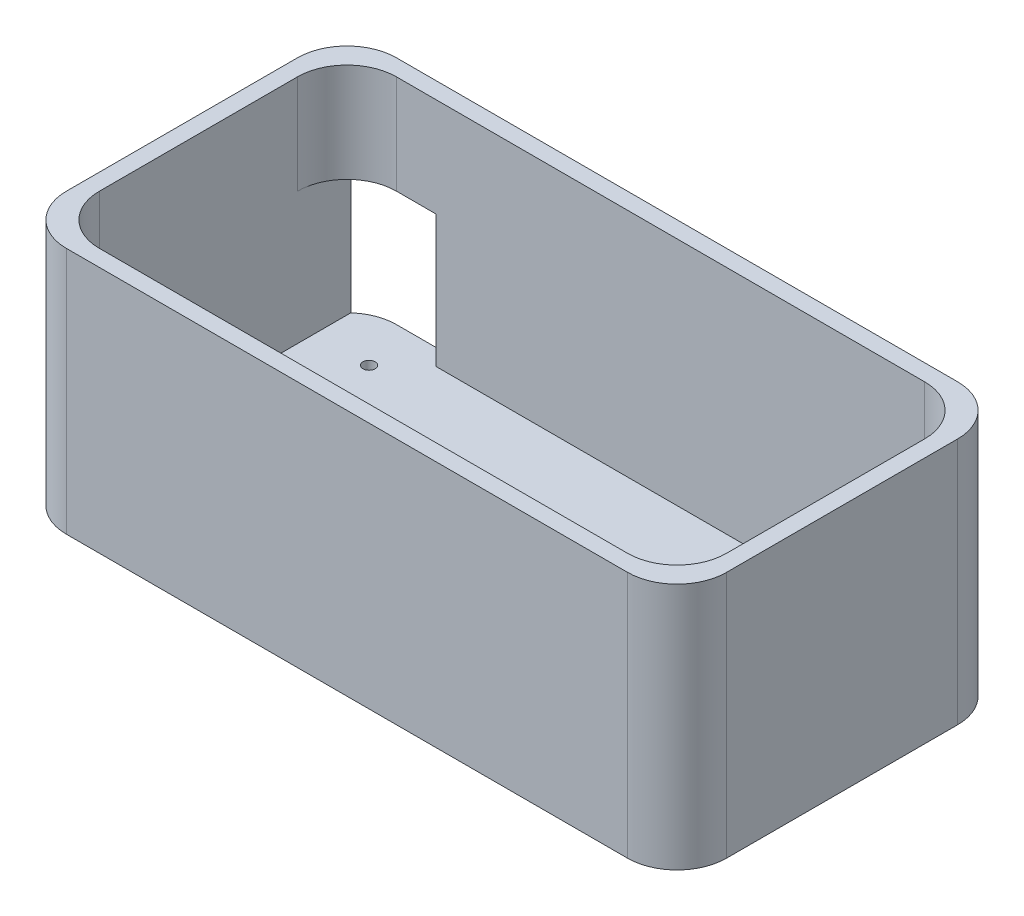
SolidWorks part; units mm, degrees
ref_plane "Front Plane" through (0, 0, 0) normal (0, 0, 1) x (1, 0, 0)
ref_plane "Top Plane" through (0, 0, 0) normal (0, 1, 0) x (1, 0, 0)
ref_plane "Right Plane" through (0, 0, 0) normal (1, 0, 0) x (0, 0, -1)
sketch "Sketch1" plane through (0, 0, 0) normal (0, 1, 0) x (1, 0, 0)
  line L1 (-100, 50) -> (100, 50)
  line L2 (-100, 50) -> (-100, -50)
  line L3 (-100, -50) -> (100, -50)
  line L4 (100, 50) -> (100, -50)
  line L5 (-100, 50) -> (100, -50) construction
  line L6 (-100, -50) -> (100, 50) construction
  point P0 (0, 0)
  dimension "D1" = 200
  dimension "D2" = 100
extrude "Boss-Extrude1" add sketch "Sketch1" along normal blind 5
sketch "Sketch2" plane through (0, 5, 0) normal (0, 1, 0) x (1, 0, 0)
  line L1 (-100, 50) -> (100, 50)
  line L2 (-100, 50) -> (-100, -50)
  line L3 (-100, -50) -> (100, -50)
  line L4 (100, 50) -> (100, -50)
  line L5 (-100, 50) -> (100, -50) construction
  line L6 (-100, -50) -> (100, 50) construction
  line L7 (-95, 45) -> (95, 45)
  line L8 (-95, 45) -> (-95, -45)
  line L9 (-95, -45) -> (95, -45)
  line L10 (95, 45) -> (95, -45)
  line L11 (-95, 45) -> (95, -45) construction
  line L12 (-95, -45) -> (95, 45) construction
  point P0 (0, 0)
  point P5 (0, 0)
  dimension "D1" = 5
  dimension "D2" = 5
extrude "Boss-Extrude2" add sketch "Sketch2" along normal blind 70
sketch "Sketch3" plane through (0, 0, -45) normal (0, 0, 1) x (1, 0, 0)
  line L1 (-95, 5) -> (-68, 5)
  line L2 (-95, 5) -> (-95, 45)
  line L3 (-95, 45) -> (-68, 45)
  line L4 (-68, 5) -> (-68, 45)
  dimension "D1" = 40
  dimension "D2" = 27
extrude "Cut-Extrude1" cut sketch "Sketch3" against normal through all
fillet "Fillet1" radius 15 8 edges at (95, 40, 45) (95, 40, -45) (100, 37.5, -50) (-100, 37.5, -50) (-95, 60, -45) (-95, 40, 45) (100, 37.5, 50) (-100, 37.5, 50)
sketch "Sketch4" plane through (0, 5, 0) normal (0, 1, 0) x (1, 0, 0)
  line L0 (90.6066, 40.6066) -> (-90.6066, -40.6066) construction
  line L1 (-90.6066, 40.6066) -> (90.6066, -40.6066) construction
  line L2 (0, 0) -> (0, 43.0974) construction
  line L3 (0, 0) -> (43.6418, 0) construction
  arc A0 (95, 30) -> (80, 45) centre (80, 30) ccw construction
  arc A1 (-95, -30) -> (-80, -45) centre (-80, -30) ccw construction
  arc A2 (-80, 45) -> (-95, 30) centre (-80, 30) ccw construction
  arc A3 (80, -45) -> (95, -30) centre (80, -30) ccw construction
  circle A4 centre (78.4791, 35.1715) radius 1.85
  circle A5 centre (-78.4791, 35.1715) radius 1.85
  circle A6 centre (78.4791, -35.1715) radius 1.85
  circle A7 centre (-78.4791, -35.1715) radius 1.85
  dimension "D1" = 86
  dimension "D2" = 3.7
extrude "Cut-Extrude2" cut sketch "Sketch4" against normal through all
